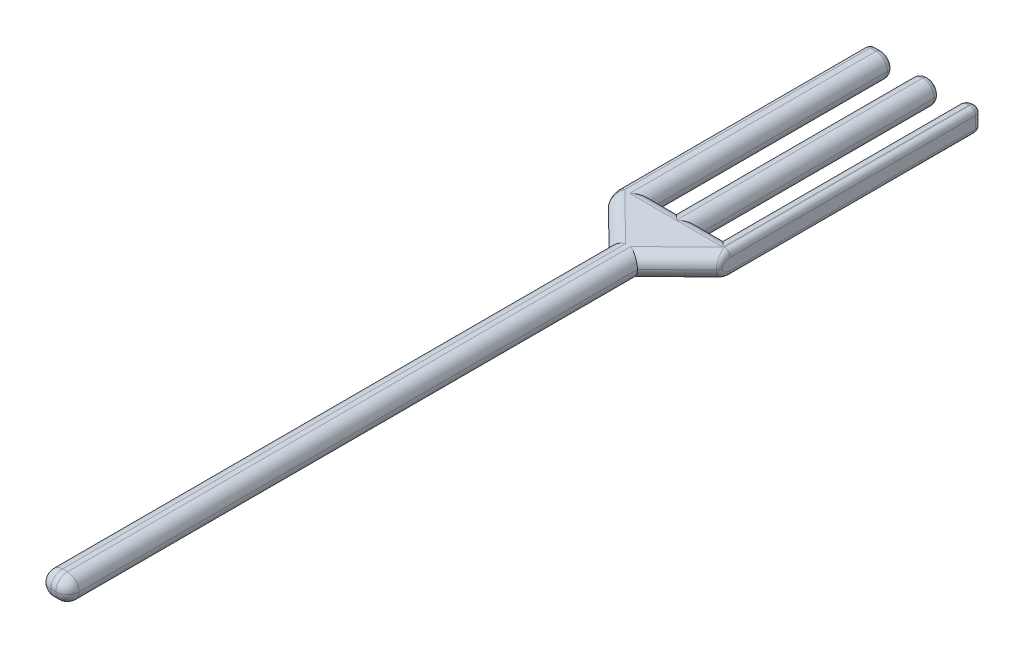
SolidWorks part; units mm, degrees
ref_plane "Front Plane" through (0, 0, 0) normal (0, 0, 1) x (1, 0, 0)
ref_plane "Top Plane" through (0, 0, 0) normal (0, 1, 0) x (1, 0, 0)
ref_plane "Right Plane" through (0, 0, 0) normal (1, 0, 0) x (0, 0, -1)
sketch "Sketch1" plane through (0, 0, 0) normal (0, 1, 0) x (1, 0, 0)
  line L0 (0, 0) -> (0, 120.9667)
  line L1 (0, 120.9667) -> (6.1704, 120.9667)
  line L2 (6.1704, 120.9667) -> (6.1704, -3.4933)
  line L3 (6.1704, -3.4933) -> (-3.6268, -3.4933)
  line L4 (0, 120.9667) -> (-9.0696, 129.8567)
  line L5 (-9.0696, 129.8567) -> (-9.0696, 187.0067)
  line L6 (-9.0696, 187.0067) -> (-3.9896, 187.0067)
  line L7 (-3.9896, 187.0067) -> (-3.9896, 134.5374)
  line L8 (-3.9896, 134.5374) -> (1.0904, 134.5374)
  line L9 (1.0904, 134.5374) -> (1.0904, 187.0067)
  line L10 (1.0904, 187.0067) -> (6.1704, 187.0067)
  line L11 (6.1704, 187.0067) -> (6.1704, 134.5374)
  line L12 (6.1704, 134.5374) -> (11.2504, 134.5374)
  line L13 (11.2504, 134.5374) -> (11.2504, 187.0067)
  line L14 (11.2504, 187.0067) -> (15.24, 187.0067)
  line L15 (15.24, 187.0067) -> (15.24, 129.8567)
  line L16 (6.1704, 120.9667) -> (15.24, 129.8567)
  line L17 (0, 0) -> (0, -3.4933)
  dimension "D2" = 12.7
  dimension "D3" = 12.7
  dimension "D4" = 8.89
  dimension "D5" = 8.89
  dimension "D6" = 5.08
  dimension "D7" = 5.08
  dimension "D8" = 5.08
  dimension "D9" = 5.08
extrude "Boss-Extrude1" add sketch "Sketch1" along normal blind 5.08 contours L0 L17 L3 L2 L1 | L1 L16 L15 L14 L13 L12 L11 L10 L9 L8 L7 L6 L5 L4 region at (3.0852, 0, -58.7367) region at (2.7921, 0, -152.783)
fillet "Fillet2" radius 2.54 2 edges at (6.1704, 5.08, -58.7367) (0, 0, -58.7367)
fillet "Fillet3" radius 2.54 2 edges at (6.1704, 0, -58.7367) (0, 5.08, -58.7367)
fillet "Fillet4" radius 2.54 6 edges at (0.7439, 0.7439, 3.4933) (0.7439, 4.3361, 3.4933) (3.0852, 5.08, 3.4933) (5.4264, 4.3361, 3.4933) (5.4264, 0.7439, 3.4933) (3.0852, 0, 3.4933)
fillet "Fillet5" radius 2.54 4 edges at (-3.2648, 0, -124.1669) (9.4352, 0, -124.1669) (9.4352, 5.08, -124.1669) (-3.2648, 5.08, -124.1669)
fillet "Fillet6" radius 2.54 12 edges at (11.2504, 5.08, -160.7721) (11.2504, 0, -160.7721) (1.0904, 5.08, -160.7721) (1.0904, 0, -160.7721) (6.1704, 0, -160.7721) (6.1704, 5.08, -160.7721) (-3.9896, 5.08, -160.7721) (-3.9896, 0, -160.7721) (8.7104, 0, -134.5374) (8.7104, 5.08, -134.5374) (-1.4496, 0, -134.5374) (-1.4496, 5.08, -134.5374)
fillet "Fillet8" radius 1.27 22 edges at (-7.7996, 5.08, -187.0067) (14.5152, 0, -187.0067) (14.5152, 5.08, -187.0067) (-9.0696, 5.08, -160.2101) (-4.7336, 0.7439, -187.0067) (-4.7336, 4.3361, -187.0067) (-9.0696, 2.54, -187.0067) (-7.7996, 0, -187.0067) (5.4264, 0.7439, -187.0067) (1.8343, 0.7439, -187.0067) (1.8343, 4.3361, -187.0067) (5.4264, 4.3361, -187.0067) (11.9943, 0.7439, -187.0067) (11.9943, 4.3361, -187.0067) (15.24, 2.54, -187.0067) (15.24, 0.7439, -130.8984) (15.24, 4.3361, -130.8984) (15.24, 5.08, -160.2101) (15.24, 0, -160.2101) (-9.0696, 0.7439, -130.8984) (-9.0696, 4.3361, -130.8984) (-9.0696, 0, -160.2101)
